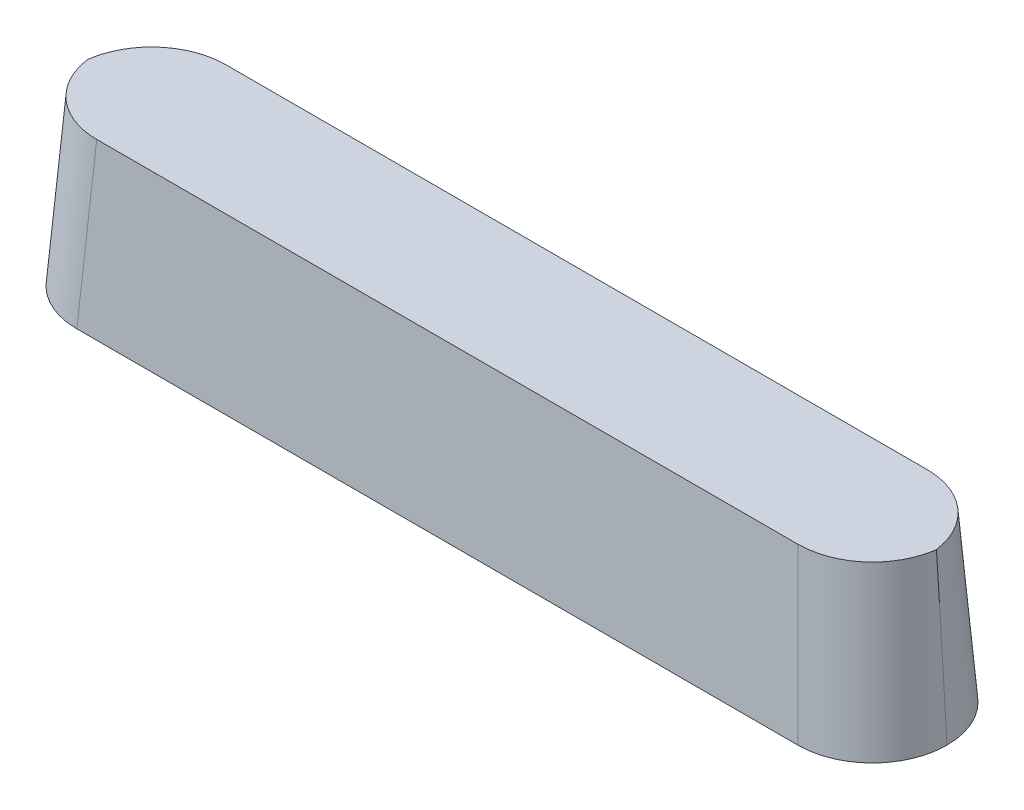
SolidWorks part; units mm, degrees
ref_plane "前视基准面" through (0, 0, 0) normal (0, 0, 1) x (1, 0, 0)
ref_plane "上视基准面" through (0, 0, 0) normal (0, 1, 0) x (1, 0, 0)
ref_plane "右视基准面" through (0, 0, 0) normal (1, 0, 0) x (0, 0, -1)
sketch "草图1" plane through (0, 0, 0) normal (0, 1, 0) x (1, 0, 0)
  line L1 (87.5, -15) -> (-87.5, -15)
  line L2 (87.5, -15) -> (87.5, 15)
  line L3 (87.5, 15) -> (-87.5, 15)
  line L4 (-87.5, -15) -> (-87.5, 15)
  line L5 (87.5, -15) -> (-87.5, 15) construction
  line L6 (87.5, 15) -> (-87.5, -15) construction
  point P0 (0, 0)
  dimension "D1" = 175
  dimension "D2" = 30
ref_plane "基准面1" through (0, 33, 0) normal (0, 1, 0) x (1, 0, 0)
sketch "草图2" plane through (0, 33, 0) normal (0, 1, 0) x (1, 0, 0)
  line L0 (87.5, 15) -> (-87.5, 15) construction
  line L1 (87.5, 15) -> (-87.5, 15) construction
  line L2 (87.5, -15) -> (87.5, 15) construction
  line L3 (87.5, -15) -> (-87.5, -15) construction
  line L4 (-87.5, -15) -> (-87.5, 15) construction
  line L5 (87.5, -15) -> (87.5, 15) construction
  line L6 (87.5, -15) -> (-87.5, -15) construction
  line L7 (-87.5, -15) -> (-87.5, 15) construction
  line L8 (85.5, 13) -> (-85.5, 13)
  line L9 (-85.5, -13) -> (-85.5, 13)
  line L10 (85.5, -13) -> (-85.5, -13)
  line L11 (85.5, -13) -> (85.5, 13)
  dimension "D1" = 2
loft "放样1" add profiles "草图1", "草图2" connector at (-87.5, 0, 15) connector at (-85.5, 33, 13)
fillet "圆角1" radius 15 4 edges
